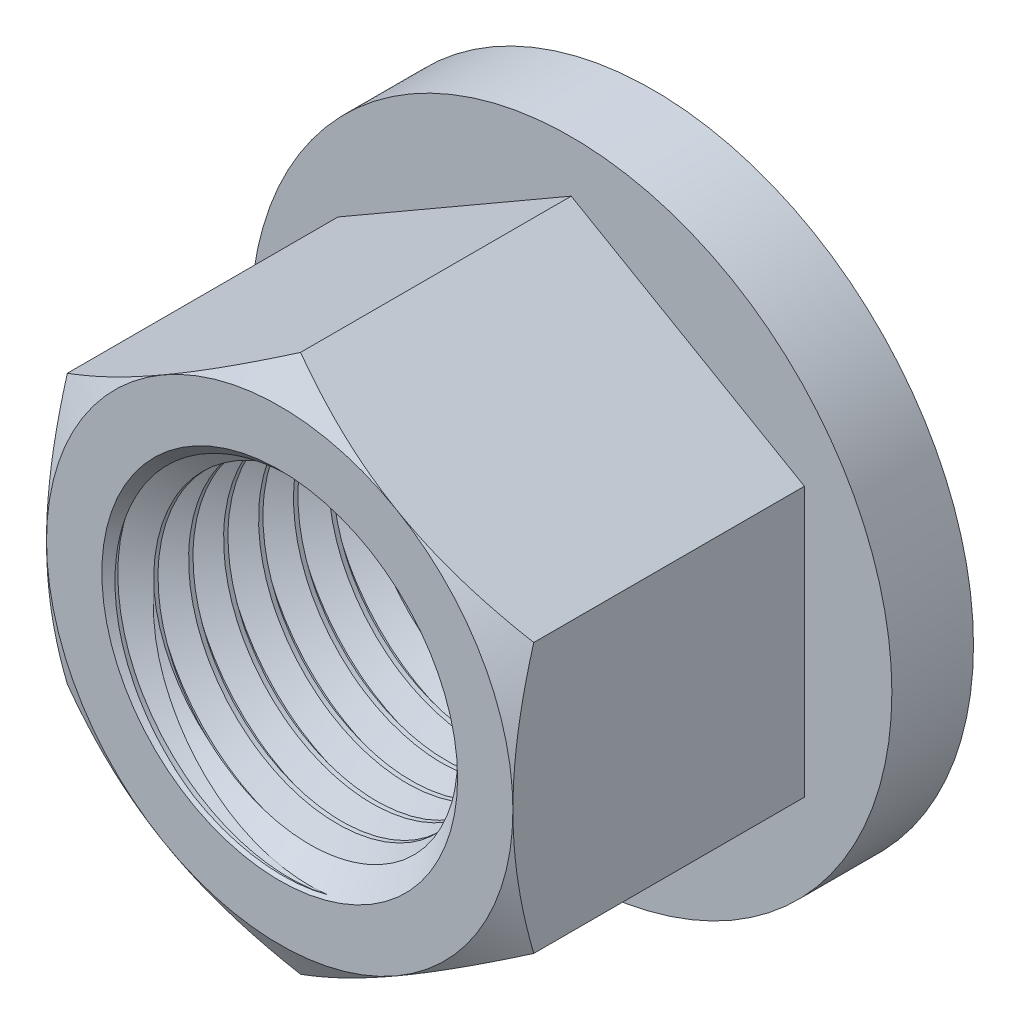
SolidWorks part; units mm, degrees
ref_plane "Front Plane" through (0, 0, 0) normal (0, 0, 1) x (1, 0, 0)
ref_plane "Top Plane" through (0, 0, 0) normal (0, 1, 0) x (1, 0, 0)
ref_plane "Right Plane" through (0, 0, 0) normal (1, 0, 0) x (0, 0, -1)
sketch "Sketch1" plane through (0, 0, 0) normal (0, 0, 1) x (1, 0, 0)
  line L1 (0, 23.094) -> (-20, 11.547)
  line L2 (-20, 11.547) -> (-20, -11.547)
  line L3 (-20, -11.547) -> (0, -23.094)
  line L4 (0, -23.094) -> (20, -11.547)
  line L5 (20, -11.547) -> (20, 11.547)
  line L6 (20, 11.547) -> (0, 23.094)
  circle A0 centre (0, 0) radius 20 construction
  dimension "Hex" = 40
extrude "Extrude1" add sketch "Sketch1" against normal blind 32
sketch "Sketch13" plane through (0, 0, -32) normal (0, 0, -1) x (-1, 0, 0)
  circle A0 centre (0, 0) radius 27.5
  dimension "Flange od" = 55
extrude "Extrude3" add sketch "Sketch13" against normal blind 7
sketch "Sketch2" plane through (0, 0, 0) normal (0, 0, 1) x (1, 0, 0)
  circle A0 centre (0, 0) radius 20 construction
  circle A1 centre (0, 0) radius 20
extrude "Cut-Extrude1" cut sketch "Sketch2" against normal through all draft 60 flip side to cut
sketch "Sketch4" plane through (0, 0, 0) normal (0, 0, 1) x (1, 0, 0)
  circle A0 centre (0, 0) radius 15
  dimension "Thread Dia" = 30
extrude "Cut-Extrude3" cut sketch "Sketch4" against normal through all
sketch "Sketch7" plane through (0, 0, 0) normal (0, 0, 1) x (1, 0, 0)
  circle A4 centre (0, 0) radius 15.254
  circle A5 centre (0, 0) radius 15.254
  dimension "D1" = 0.254
sketch "Sketch8" plane through (0, 0, -32) normal (0, 0, -1) x (-1, 0, 0)
  circle A1 centre (0, 0) radius 15.254
  circle A2 centre (0, 0) radius 15.254 construction
sketch "Sketch5" plane through (0, 0, 0) normal (0, 0, 1) x (1, 0, 0)
  circle A0 centre (0, 0) radius 15 construction
  circle A1 centre (0, 0) radius 15
curve "Helix/Spiral1" pitch 3 height 35 turns 11.6667 parameters "pitch"=3
sketch "Sketch9" plane through (0, 0, 0) normal (1, 0, 0) x (0, 0, -1)
  line L0 (-1.5, 15) -> (-1.125, 15)
  line L1 (-1.125, 15) -> (0, 13.0514)
  line L2 (-1.5, 15) -> (-2.625, 13.0514)
  line L3 (-2.625, 13.0514) -> (0, 13.0514)
  line L4 (-1.3125, 15) -> (-1.3125, 13.0514) construction
  line L5 (-2.0625, 14.0257) -> (-0.5625, 14.0257) construction
  line L7 (0, 13.0514) -> (0, 15) construction
  line L8 (0, 15) -> (0, -15) construction
  dimension "D1" = 0.375
  dimension "D2" = 1.5
  dimension "D3" = 60
sketch "Sketch12" plane through (0, 0, 0) normal (0, 0, 1) x (1, 0, 0)
  circle A0 centre (0, 0) radius 13.0514
  circle A1 centre (0, 0) radius 15 construction
  circle A2 centre (0, 0) radius 15
extrude "Extrude2" add sketch "Sketch12" against normal up to surface (32 mm away) up to face at (15, 0, -32)
sweep "Cut-Sweep1" cut profiles "Sketch9" path "Helix/Spiral1"
extrude "Cut-Extrude6" cut sketch "Sketch7" against normal through all draft 45
extrude "Cut-Extrude7" cut sketch "Sketch8" against normal through all draft 45
equation "\"D2@Sketch9\" = \"pitch@Helix/Spiral1\"*.5"
equation "\"D3@Helix/Spiral1\" = \"pitch@Helix/Spiral1\"+\"Height@Extrude1\""
equation "\"D1@Sketch9\" = \"pitch@Helix/Spiral1\"*.125"
